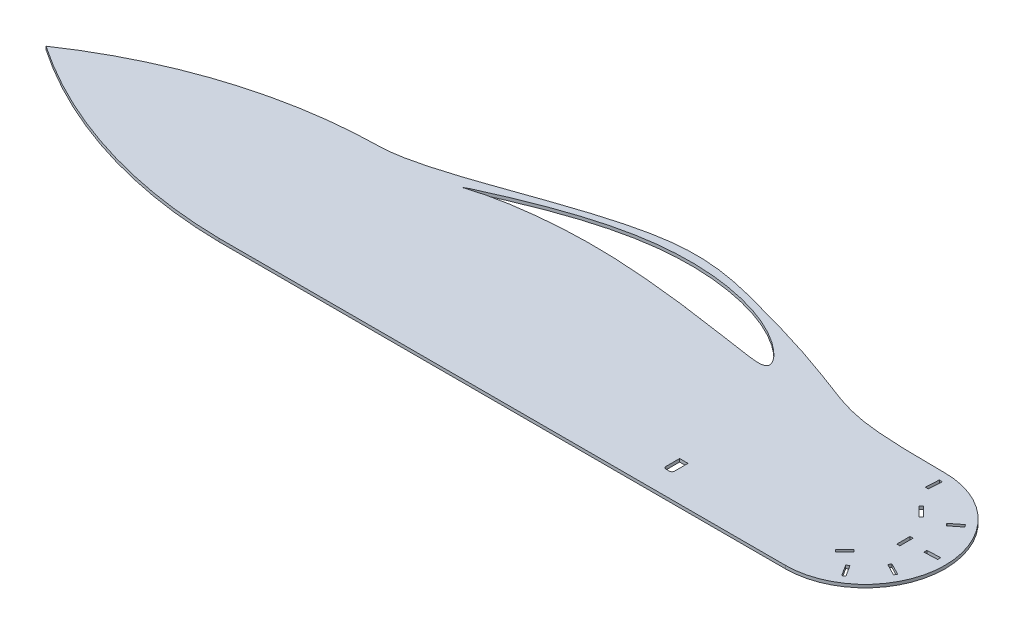
SolidWorks part; units mm, degrees
ref_plane "Front Plane" through (0, 0, 0) normal (0, 0, 1) x (1, 0, 0)
ref_plane "Top Plane" through (0, 0, 0) normal (0, 1, 0) x (1, 0, 0)
ref_plane "Right Plane" through (0, 0, 0) normal (1, 0, 0) x (0, 0, -1)
sketch "Sketch1" plane through (0, 0, 0) normal (0, 1, 0) x (1, 0, 0)
  line L0 (800, 78) -> (0, 78) construction
  line L1 (247.0699, 0) -> (800, 0)
  line L2 (0, 0) -> (0, 156) construction
  arc A0 (800, 156) -> (800, 0) centre (800, 78) cw
  arc A1 (247.0699, 156) -> (0, 78) centre (253.6132, -295.0311) ccw
  arc A2 (247.0699, 0) -> (0, 78) centre (253.6132, 451.0311) cw
  spline S0 degree 3 poles (800, 156) (666.9069, 156) (724.4527, 168.8171) (449.2718, 236.2021) (302.0218, 156.7972) (247.0699, 156) knots 0 0 0 0 0.676894 0.776894 1 1 1 1
  point P12 (458.8214, 222.386)
  point P13 (0, 0)
  point P14 (493.0584, 221.485)
  point P15 (481.3458, 222.386)
  point P16 (501.1672, 218.7821)
  dimension "D1" = 800
  dimension "D2" = 156
  dimension "D3" = 247.0699
extrude "Boss-Extrude1" add sketch "Sketch1" along normal blind 3
sketch "Sketch2" plane through (0, 0, 0) normal (0, -1, 0) x (1, 0, 0)
  line L4 (824.3506, -106.2174) -> (815.1582, -115.4098)
  line L5 (815.1582, -115.4098) -> (817.2796, -117.5311)
  line L6 (817.2796, -117.5311) -> (826.472, -108.3387)
  line L7 (826.472, -108.3387) -> (824.3506, -106.2174)
  line L8 (824.3506, -106.2174) -> (815.1582, -115.4098)
  line L9 (815.1582, -115.4098) -> (817.2796, -117.5311)
  line L10 (817.2796, -117.5311) -> (826.472, -108.3387)
  line L11 (826.472, -108.3387) -> (824.3506, -106.2174)
  line L20 (831.7847, -31.2816) -> (838.8093, -20.343)
  line L21 (838.8093, -20.343) -> (836.285, -18.7219)
  line L22 (836.285, -18.7219) -> (829.2604, -29.6606)
  line L23 (829.2604, -29.6606) -> (831.7847, -31.2816)
  line L24 (831.7847, -31.2816) -> (838.8093, -20.343)
  line L25 (838.8093, -20.343) -> (836.285, -18.7219)
  line L26 (836.285, -18.7219) -> (829.2604, -29.6606)
  line L27 (829.2604, -29.6606) -> (831.7847, -31.2816)
  line L28 (839.4564, -85.3169) -> (839.4564, -72.3169)
  line L29 (839.4564, -72.3169) -> (836.4564, -72.3169)
  line L30 (836.4564, -72.3169) -> (836.4564, -85.3169)
  line L31 (836.4564, -85.3169) -> (839.4564, -85.3169)
  line L32 (839.4564, -85.3169) -> (839.4564, -72.3169)
  line L33 (839.4564, -72.3169) -> (836.4564, -72.3169)
  line L34 (836.4564, -72.3169) -> (836.4564, -85.3169)
  line L35 (836.4564, -85.3169) -> (839.4564, -85.3169)
  line L37 (322.8858, -161.8367) -> (322.8858, -161.8697)
  line L38 (322.8858, -161.8367) -> (322.8858, -161.8697)
  line L40 (658.0699, -25.4734) -> (658.0699, -38.6734)
  line L41 (663.7699, -22.9734) -> (660.5699, -22.9734)
  line L42 (666.2699, -38.6734) -> (666.2699, -25.4734)
  line L43 (658.0699, -38.6734) -> (666.2699, -38.6734)
  line L44 (658.0699, -25.4734) -> (658.0699, -38.6734)
  line L45 (663.7699, -22.9734) -> (660.5699, -22.9734)
  line L46 (666.2699, -38.6734) -> (666.2699, -25.4734)
  line L47 (658.0699, -38.6734) -> (666.2699, -38.6734)
  line L188 (802.1648, -134.464) -> (803.0075, -147.4367) construction
  line L189 (803.0075, -147.4367) -> (806.0011, -147.2422) construction
  line L190 (806.0011, -147.2422) -> (805.1584, -134.2695) construction
  line L191 (805.1584, -134.2695) -> (802.1648, -134.464) construction
  line L192 (843.3276, -114.271) -> (853.5139, -122.3482) construction
  line L193 (853.5139, -122.3482) -> (855.3778, -119.9975) construction
  line L194 (855.3778, -119.9975) -> (845.1916, -111.9204) construction
  line L195 (845.1916, -111.9204) -> (843.3276, -114.271) construction
  line L196 (856.3804, -81.7584) -> (869.37, -82.2784) construction
  line L197 (869.37, -82.2784) -> (869.49, -79.2808) construction
  line L198 (869.49, -79.2808) -> (856.5004, -78.7608) construction
  line L199 (856.5004, -78.7608) -> (856.3804, -81.7584) construction
  line L200 (850.8133, -53.284) -> (862.3486, -47.2894) construction
  line L201 (862.3486, -47.2894) -> (860.9653, -44.6274) construction
  line L202 (860.9653, -44.6274) -> (849.4299, -50.622) construction
  line L203 (849.4299, -50.622) -> (850.8133, -53.284) construction
  line L204 (822.4088, -44.7346) -> (813.2164, -35.5422) construction
  line L205 (813.2164, -35.5422) -> (811.0951, -37.6635) construction
  line L206 (811.0951, -37.6635) -> (820.2875, -46.8559) construction
  line L207 (820.2875, -46.8559) -> (822.4088, -44.7346) construction
  line L208 (802.1648, -134.464) -> (803.0075, -147.4367)
  line L209 (803.0075, -147.4367) -> (806.0011, -147.2422)
  line L210 (806.0011, -147.2422) -> (805.1584, -134.2695)
  line L211 (805.1584, -134.2695) -> (802.1648, -134.464)
  line L212 (843.3276, -114.271) -> (853.5139, -122.3482)
  line L213 (853.5139, -122.3482) -> (855.3778, -119.9975)
  line L214 (855.3778, -119.9975) -> (845.1916, -111.9204)
  line L215 (845.1916, -111.9204) -> (843.3276, -114.271)
  line L216 (856.3804, -81.7584) -> (869.37, -82.2784)
  line L217 (869.37, -82.2784) -> (869.49, -79.2808)
  line L218 (869.49, -79.2808) -> (856.5004, -78.7608)
  line L219 (856.5004, -78.7608) -> (856.3804, -81.7584)
  line L220 (850.8133, -53.284) -> (862.3486, -47.2894)
  line L221 (862.3486, -47.2894) -> (860.9653, -44.6274)
  line L222 (860.9653, -44.6274) -> (849.4299, -50.622)
  line L223 (849.4299, -50.622) -> (850.8133, -53.284)
  line L224 (822.4088, -44.7346) -> (813.2164, -35.5422)
  line L225 (813.2164, -35.5422) -> (811.0951, -37.6635)
  line L226 (811.0951, -37.6635) -> (820.2875, -46.8559)
  line L227 (820.2875, -46.8559) -> (822.4088, -44.7346)
  arc A2 (660.5699, -22.9734) -> (658.0699, -25.4734) centre (660.5699, -25.4734) ccw
  arc A3 (666.2699, -25.4734) -> (663.7699, -22.9734) centre (663.7699, -25.4734) ccw
  arc A4 (660.5699, -22.9734) -> (658.0699, -25.4734) centre (660.5699, -25.4734) ccw
  arc A5 (666.2699, -25.4734) -> (663.7699, -22.9734) centre (663.7699, -25.4734) ccw
  spline S1 degree 3 poles (-1380.4161, -2630.0615) (300.1014, -104.4038) (302.1555, -149.7011) (325.9799, -163.7955) (329.0392, -165.3528) (333.0995, -167.1553) (338.0748, -169.3556) (343.9889, -171.9478) (353.6504, -176.0488) (364.3874, -180.5034) (376.1271, -185.1263) (385.8755, -188.7675) (396.136, -192.3645) (410.5289, -197.0178) (425.3632, -201.1893) (440.5325, -204.6531) (452.0326, -206.8377) (463.5542, -208.5454) (475.0656, -209.7647) (486.5379, -210.4642) (497.9272, -210.6618) (509.1695, -210.3395) (523.7372, -209.2712) (537.8966, -207.2749) (551.5111, -204.4023) (561.1377, -201.8946) (570.2647, -199.0446) (578.8275, -195.8625) (586.7694, -192.3996) (594.0309, -188.7037) (600.5639, -184.8597) (606.3354, -180.9818) (611.3138, -177.1606) (615.4633, -173.459) (618.7631, -169.9576) (621.168, -166.7557) (622.5463, -164.0939) (622.9881, -162.0129) (622.6817, -160.2689) (621.1521, -158.8428) (618.6166, -158.1794) (615.3065, -157.9718) (611.1609, -158.2078) (606.2021, -158.7819) (600.4431, -159.6086) (593.9164, -160.589) (586.6617, -161.6568) (578.7346, -162.8457) (570.1854, -164.1278) (557.7199, -165.9889) (544.6185, -167.8669) (523.5463, -170.6552) (505.2322, -172.7454) (482.7288, -174.76) (463.5943, -176.0723) (444.4197, -176.6954) (429.1533, -176.6942) (417.8851, -176.4379) (406.8606, -175.9173) (396.1694, -175.1735) (385.902, -174.2295) (376.1453, -173.1318) (366.9892, -171.8877) (358.5208, -170.5334) (350.8258, -169.0982) (343.9818, -167.639) (338.0513, -166.2044) (333.0873, -164.7805) (329.0904, -163.4875) (326.0405, -162.5701) (300.7369, -156.1716) (269.4152, -183.1311) (878.0602, 2785.2585) knots -0.121434 -0.121434 -0.121434 -0.121434 0.001413 0.005226 0.010781 0.017816 0.026461 0.036791 0.048686 0.076639 0.092363 0.109003 0.126387 0.144339 0.181313 0.200023 0.218713 0.237261 0.255692 0.274037 0.292193 0.310133 0.327788 0.362002 0.378421 0.394287 0.409543 0.424114 0.437938 0.450942 0.463044 0.474154 0.484165 0.493024 0.500713 0.507126 0.51213 0.514904 0.517171 0.520262 0.524245 0.529498 0.536092 0.544061 0.553363 0.563905 0.575615 0.58842 0.602227 0.616944 0.648676 0.665501 0.718564 0.736789 0.773513 0.810245 0.828489 0.846493 0.864125 0.881249 0.897725 0.913415 0.928184 0.941897 0.954411 0.965603 0.97535 0.983576 0.990285 0.995433 0.9988 1.114983 1.114983 1.114983 1.114983 only from (322.8858, -161.8697) to (322.8858, -161.8367)
  spline S2 degree 3 poles (322.8858, -161.8697) (323.1309, -162.035) (324.0372, -162.6462) (325.9799, -163.7955) (329.0392, -165.3528) (333.0995, -167.1553) (338.0748, -169.3556) (343.9889, -171.9478) (353.6504, -176.0488) (364.3874, -180.5034) (376.1271, -185.1263) (385.8755, -188.7675) (396.136, -192.3645) (410.5289, -197.0178) (425.3632, -201.1893) (440.5325, -204.6531) (452.0326, -206.8377) (463.5542, -208.5454) (475.0656, -209.7647) (486.5379, -210.4642) (497.9272, -210.6618) (509.1695, -210.3395) (523.7372, -209.2712) (537.8966, -207.2749) (551.5111, -204.4023) (561.1377, -201.8946) (570.2647, -199.0446) (578.8275, -195.8625) (586.7694, -192.3996) (594.0309, -188.7037) (600.5639, -184.8597) (606.3354, -180.9818) (611.3138, -177.1606) (615.4633, -173.459) (618.7631, -169.9576) (621.168, -166.7557) (622.5463, -164.0939) (622.9881, -162.0129) (622.6817, -160.2689) (621.1521, -158.8428) (618.6166, -158.1794) (615.3065, -157.9718) (611.1609, -158.2078) (606.2021, -158.7819) (600.4431, -159.6086) (593.9164, -160.589) (586.6617, -161.6568) (578.7346, -162.8457) (570.1854, -164.1278) (557.7199, -165.9889) (544.6185, -167.8669) (523.5463, -170.6552) (505.2322, -172.7454) (482.7288, -174.76) (463.5943, -176.0723) (444.4197, -176.6954) (429.1533, -176.6942) (417.8851, -176.4379) (406.8606, -175.9173) (396.1694, -175.1735) (385.902, -174.2295) (376.1453, -173.1318) (366.9892, -171.8877) (358.5208, -170.5334) (350.8258, -169.0982) (343.9818, -167.639) (338.0513, -166.2044) (333.0873, -164.7805) (329.0904, -163.4875) (326.0405, -162.5701) (324.0691, -162.0716) (323.132, -161.8855) (322.8858, -161.8367) knots 0 0 0 0 0.001413 0.005226 0.010781 0.017816 0.026461 0.036791 0.048686 0.076639 0.092363 0.109003 0.126387 0.144339 0.181313 0.200023 0.218713 0.237261 0.255692 0.274037 0.292193 0.310133 0.327788 0.362002 0.378421 0.394287 0.409543 0.424114 0.437938 0.450942 0.463044 0.474154 0.484165 0.493024 0.500713 0.507126 0.51213 0.514904 0.517171 0.520262 0.524245 0.529498 0.536092 0.544061 0.553363 0.563905 0.575615 0.58842 0.602227 0.616944 0.648676 0.665501 0.718564 0.736789 0.773513 0.810245 0.828489 0.846493 0.864125 0.881249 0.897725 0.913415 0.928184 0.941897 0.954411 0.965603 0.97535 0.983576 0.990285 0.995433 0.9988 1 1 1 1
  dimension "D1" = 0
  dimension "D2" = 0
  dimension "D3" = 0
  dimension "D4" = 0
  dimension "D5" = 0
extrude "Cut-Extrude1" cut sketch "Sketch2" against normal through all
